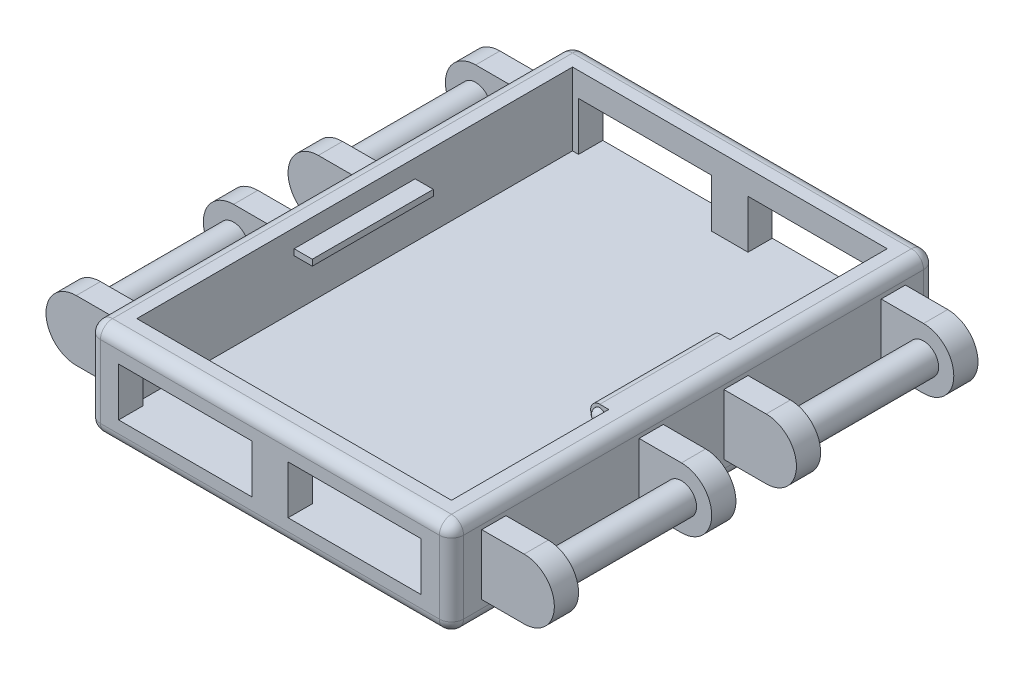
SolidWorks part; units mm, degrees
ref_plane "Front Plane" through (0, 0, 0) normal (0, 0, 1) x (1, 0, 0)
ref_plane "Top Plane" through (0, 0, 0) normal (0, 1, 0) x (1, 0, 0)
ref_plane "Right Plane" through (0, 0, 0) normal (1, 0, 0) x (0, 0, -1)
sketch "Sketch2" plane through (0, 0, 0) normal (0, 1, 0) x (1, 0, 0)
  line L1 (-30, 40) -> (30, 40)
  line L2 (-30, 40) -> (-30, -40)
  line L3 (-30, -40) -> (30, -40)
  line L4 (30, 40) -> (30, -40)
  line L5 (-30, 40) -> (30, -40) construction
  line L6 (-30, -40) -> (30, 40) construction
  point P0 (0, 0)
  dimension "D1" = 80
  dimension "D2" = 60
extrude "Boss-Extrude2" add sketch "Sketch2" along normal blind 16 contours L2 L3 L4 L1
sketch "Sketch6" plane through (0, 16, 0) normal (0, 1, 0) x (1, 0, 0)
  line L1 (-26, 36) -> (26, 36)
  line L2 (-26, 36) -> (-26, -36)
  line L3 (-26, -36) -> (26, -36)
  line L4 (26, 36) -> (26, -36)
  line L5 (-26, 36) -> (26, -36) construction
  line L6 (-26, -36) -> (26, 36) construction
  point P0 (0, 0)
extrude "Cut-Extrude1" cut sketch "Sketch6" against normal blind 12
sketch "Sketch7" plane through (0, 0, -40) normal (0, 0, -1) x (-1, 0, 0)
  line L0 (-30, 16) -> (-30, 0) construction
  line L1 (-3, 12) -> (-25, 12)
  line L2 (-3, 12) -> (-3, 4)
  line L3 (-3, 4) -> (-25, 4)
  line L4 (-25, 12) -> (-25, 4)
  line L5 (-3, 12) -> (-25, 4) construction
  line L6 (-3, 4) -> (-25, 12) construction
  line L7 (25, 12) -> (3, 12)
  line L8 (25, 12) -> (25, 4)
  line L9 (25, 4) -> (3, 4)
  line L10 (3, 12) -> (3, 4)
  line L11 (30, 0) -> (-30, 0) construction
  line L12 (30, 16) -> (30, 0) construction
  point P0 (-14, 8)
  dimension "D1" = 22
  dimension "D2" = 5
  dimension "D3" = 4
  dimension "D4" = 5
  dimension "D5" = 4
  dimension "D6" = 22
  dimension "D7" = 8
  dimension "D8" = 8
extrude "Cut-Extrude2" cut sketch "Sketch7" against normal blind 106 and the other way blind 16
sketch "Sketch8" plane through (30, 0, 0) normal (1, 0, 0) x (0, 0, -1)
  line L1 (-35, 3.3031) -> (-31, 3.3031)
  line L2 (-35, 3.3031) -> (-35, 13.3031)
  line L3 (-35, 13.3031) -> (-31, 13.3031)
  line L4 (-31, 3.3031) -> (-31, 13.3031)
  line L5 (-35, 3.3031) -> (-31, 13.3031) construction
  line L6 (-35, 13.3031) -> (-31, 3.3031) construction
  line L7 (-40, 16) -> (-40, 0) construction
  line L8 (-9, 3.3552) -> (-5, 3.3552)
  line L9 (-9, 3.3552) -> (-9, 13.3552)
  line L10 (-9, 13.3552) -> (-5, 13.3552)
  line L11 (-5, 3.3552) -> (-5, 13.3552)
  line L12 (0, 16) -> (0, 0)
  line L13 (40, 16) -> (-40, 16) construction
  line L14 (35, 13.3031) -> (31, 3.3031) construction
  line L15 (35, 3.3031) -> (31, 13.3031) construction
  line L16 (5, 3.3552) -> (5, 13.3552)
  line L17 (9, 13.3552) -> (5, 13.3552)
  line L18 (9, 3.3552) -> (9, 13.3552)
  line L19 (9, 3.3552) -> (5, 3.3552)
  line L20 (31, 3.3031) -> (31, 13.3031)
  line L21 (35, 13.3031) -> (31, 13.3031)
  line L22 (35, 3.3031) -> (35, 13.3031)
  line L23 (35, 3.3031) -> (31, 3.3031)
  point P0 (-33, 8.3031)
  point P24 (33, 8.3031)
  dimension "D1" = 5
  dimension "D2" = 31
  dimension "D3" = 22
ref_plane "Midsection" through (0, 0, 0) normal (1, 0, 0) x (0, 0, -1)
ref_plane "Midsection (Short)" through (0, 0, 0) normal (0, 0, -1) x (-1, 0, 0)
ref_axis "Strap Mirror" through (30, 16, 0) along (0, -1, 0)
extrude "Boss-Extrude3" add sketch "Sketch8" along normal blind 12 contours L4 L3 L2 L1 | L11 L10 L9 L8 | L18 L17 L16 L19 | L22 L21 L20 L23
fillet "Fillet1" 2 edges at (42, 13.3031, 33) (42, 3.3031, 33) type full round first side face at (36, 13.3031, 33) second side face at (36, 3.3031, 33) middle face at (42, 8.3031, 33)
fillet "Fillet2" 2 edges at (42, 13.3552, 7) (42, 3.3552, 7) type full round first side face at (36, 13.3552, 7) second side face at (36, 3.3552, 7) middle face at (42, 8.3552, 7)
fillet "Fillet3" 2 edges at (42, 13.3552, -7) (42, 3.3552, -7) type full round first side face at (36, 13.3552, -7) second side face at (36, 3.3552, -7) middle face at (42, 8.3552, -7)
fillet "Fillet4" 2 edges at (42, 13.3031, -33) (42, 3.3031, -33) type full round first side face at (36, 13.3031, -33) second side face at (36, 3.3031, -33) middle face at (42, 8.3031, -33)
sketch "Sketch9" plane through (0, 0, 31) normal (0, 0, -1) x (-1, 0, 0)
  circle A0 centre (-37, 8.3031) radius 2.5
  dimension "D1" = 5
extrude "Boss-Extrude4" add sketch "Sketch9" along normal blind 24 and the other way blind 2
mirror "Mirror1" about plane through (0, 0, 0) normal (0, 0, -1) of "Boss-Extrude4"
mirror "Mirror2" about plane through (0, 0, 0) normal (1, 0, 0) of "Boss-Extrude3", "Fillet1", "Fillet2", "Fillet3", "Fillet4", "Boss-Extrude4", "Mirror1"
sketch "Sketch10" plane through (-26, 0, 0) normal (1, 0, 0) x (0, 0, -1)
  line L0 (0, -8.8) -> (0, 8.8) construction
  line L1 (-10, 13) -> (10, 13)
  line L2 (-10, 13) -> (-10, 12)
  line L3 (-10, 12) -> (10, 12)
  line L4 (10, 13) -> (10, 12)
  line L5 (-10, 13) -> (10, 12) construction
  line L6 (-10, 12) -> (10, 13) construction
  line L7 (36, 16) -> (-36, 16) construction
  point P0 (0, 12.5)
  dimension "D1" = 3
extrude "Boss-Extrude5" add sketch "Sketch10" along normal blind 2.9993
sketch "Sketch12" plane through (26, 0, 0) normal (-1, 0, 0) x (0, 0, 1)
  line L0 (0, 8.8) -> (0, -8.8) construction
  line L1 (-10, 13) -> (10, 13)
  line L2 (-10, 13) -> (-10, 16)
  line L3 (-10, 16) -> (10, 16)
  line L4 (10, 13) -> (10, 16)
  line L5 (-10, 13) -> (10, 16) construction
  line L6 (-10, 16) -> (10, 13) construction
  line L10 (36, 16) -> (-36, 16) construction
  point P0 (0, 14.5)
  dimension "D1" = 3
  dimension "D2" = 20
extrude "Boss-Extrude6" add sketch "Sketch12" along normal blind 3
sketch "Sketch13" plane through (0, 0, 10) normal (0, 0, 1) x (1, 0, 0)
  line L0 (23.5003, 14.5) -> (25.4997, 14.5)
  arc A0 (25.4997, 14.5) -> (23.5003, 14.5) centre (24.5, 14.5) cw
revolve "Revolve1" add sketch "Sketch13" angle 360 about L0
mirror "Mirror3" about plane through (0, 0, 0) normal (0, 0, -1) of "Revolve1"
fillet "Fillet6" 2 edges at (23, 16, 0) (23, 13, 0) type full round first side face at (12.25, 16, 0) second side face at (24.5, 13, 0) middle face at (23, 14.5, 0)
fillet "Fillet7" radius 2 1 edges at (-30, 16, 0) type face fillet first side face at (12.625, 16, 0) second side face at (-30, 8.3552, -7)
fillet "Fillet8" radius 2 1 edges at (1, 16, -40) type face fillet first side face at (12.625, 16, 0) second side face at (-5.6828, 9.2828, -40)
fillet "Fillet9" radius 2 1 edges at (30, 7, -40) type face fillet first side face at (30, 8.3031, -33) second side face at (1, 7, -40)
fillet "Fillet10" radius 2 1 edges at (0, 16, 40) type face fillet first side face at (12.625, 16, 0) second side face at (-14, 8, 40)
fillet "Fillet11" radius 2 1 edges at (0, 0, 40) type face fillet first side face at (-14, 8, 40) second side face at (0, 0, 0)
sketch "Sketch15" plane through (0, 0, 40) normal (0, 0, 1) x (1, 0, 0)
  line L0 (25, 4) -> (25, 12) construction
  line L1 (-3, 12) -> (-25, 12) construction
  line L2 (-3, 4) -> (-3, 12) construction
  line L3 (-6.2, 10.8) -> (-6.2, 16)
  line L4 (0, -6.6) -> (0, 6.6) construction
  line L5 (-28, 16) -> (28, 16) construction
  circle A0 centre (-4.2, 10.8) radius 1
  circle A1 centre (-4.2, 10.8) radius 2
  point P13 (0, 0)
  dimension "D1" = 2
  dimension "D2" = 1.2
  dimension "D3" = 1.2
  dimension "D4" = 4
  dimension "D5" = 4.2
  dimension "D6" = 5.2
